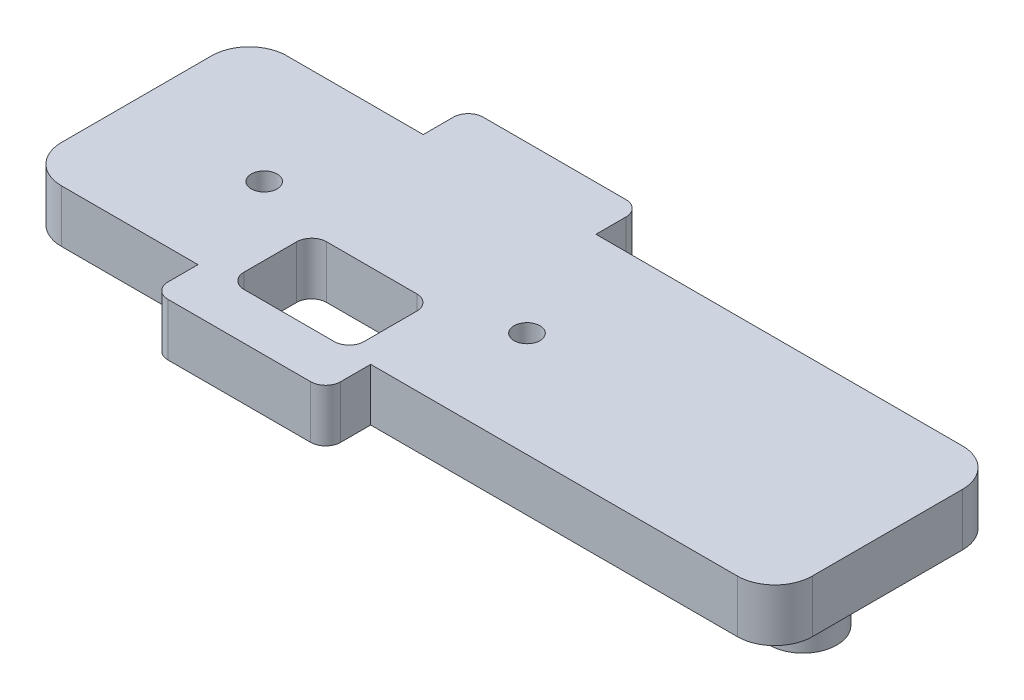
SolidWorks part; units mm, degrees
ref_plane "Front Plane" through (0, 0, 0) normal (0, 0, 1) x (1, 0, 0)
ref_plane "Top Plane" through (0, 0, 0) normal (0, 1, 0) x (1, 0, 0)
ref_plane "Right Plane" through (0, 0, 0) normal (1, 0, 0) x (0, 0, -1)
sketch "Sketch1" plane through (0, 0, 0) normal (0, 1, 0) x (1, 0, 0)
  line L1 (-45.1945, 17.8802) -> (54.8055, 17.8802)
  line L2 (-45.1945, 17.8802) -> (-45.1945, -12.1198)
  line L3 (-45.1945, -12.1198) -> (54.8055, -12.1198)
  line L4 (54.8055, 17.8802) -> (54.8055, -12.1198)
  dimension "D1" = 100
  dimension "D2" = 30
extrude "Boss-Extrude1" add sketch "Sketch1" along normal blind 7
ref_plane "Plane1" through (0, -1, 0) normal (0, -1, 0) x (-1, 0, 0)
sketch "Sketch2" plane through (0, -1, 0) normal (0, -1, 0) x (-1, 0, 0)
  line L0 (-54.8055, 2.8802) -> (57.5711, 2.8802) construction
  line L1 (-41.1646, -0.0198) -> (-44.5646, -0.0198)
  line L2 (-41.1646, -0.0198) -> (-41.1646, 5.7802)
  line L3 (-41.1646, 5.7802) -> (-44.5646, 5.7802)
  line L4 (-44.5646, -0.0198) -> (-44.5646, 5.7802)
  line L5 (-54.8055, -12.1198) -> (-54.8055, 17.8802) construction
  line L6 (-42.8646, -12.1198) -> (-42.8646, 27.765) construction
  line L8 (45.1945, -12.1198) -> (-54.8055, -12.1198) construction
  dimension "D1" = 3.4
  dimension "D2" = 5.8
  dimension "D3" = 1.7
  dimension "D4" = 2.9
extrude "Boss-Extrude2" add sketch "Sketch2" along normal blind 6 separate body
shell "Shell1" thickness 1 removed face at (42.8646, -7, -2.8802) outward yes
sketch "Sketch3" plane through (0, 0, 0) normal (0, -1, 0) x (-1, 0, 0)
  line L0 (-42.8646, -0.0198) -> (-42.8646, 11.0227) construction
  line L1 (-44.5646, -0.0198) -> (-41.1646, -0.0198) construction
  line L2 (-41.1646, 2.8802) -> (-49.8164, 2.8802) construction
  line L3 (-41.1646, -0.0198) -> (-41.1646, 5.7802) construction
  point P9 (-42.8646, 2.8802)
sketch "Sketch4" plane through (0, 0, 0) normal (0, -1, 0) x (-1, 0, 0)
  circle A0 centre (-42.9099, 3.5376) radius 4.5
  circle A1 centre (-42.9099, 3.5376) radius 3.7
extrude "Boss-Extrude3" add sketch "Sketch4" along normal blind 10
sketch "Sketch5" plane through (0, 0, 0) normal (0, -1, 0) x (-1, 0, 0)
  circle A0 centre (-42.8646, 2.8802) radius 4.25
  circle A1 centre (-42.8646, 2.8802) radius 5.5
extrude "Boss-Extrude4" add sketch "Sketch5" along normal blind 4
fillet "Fillet1" radius 5 4 edges at (-45.1945, 3.5, -17.8802) (-45.1945, 3.5, 12.1198) (54.8055, 3.5, -17.8802) (54.8055, 3.5, 12.1198)
sketch "Sketch6" plane through (0, 0, 0) normal (0, -1, 0) x (-1, 0, 0)
  line L0 (40.1945, -12.1198) -> (-49.8055, -12.1198) construction
  line L1 (22.0125, -12.1198) -> (-0.9875, -12.1198)
  line L2 (22.0125, -12.1198) -> (22.0125, -18.1198)
  line L3 (22.0125, -18.1198) -> (-0.9875, -18.1198)
  line L4 (-0.9875, -12.1198) -> (-0.9875, -18.1198)
  line L5 (45.1945, 2.8802) -> (44.2396, 2.8802) construction
  line L6 (45.1945, 12.8802) -> (45.1945, -7.1198) construction
  line L7 (22.0125, 23.8802) -> (-0.9875, 23.8802)
  line L8 (-0.9875, 17.8802) -> (-0.9875, 23.8802)
  line L9 (22.0125, 17.8802) -> (-0.9875, 17.8802)
  line L10 (22.0125, 17.8802) -> (22.0125, 23.8802)
  dimension "D1" = 6
  dimension "D2" = 23
extrude "Boss-Extrude5" add sketch "Sketch6" against normal up to surface (7 mm away) up to face at (4.8055, 7, -2.8802)
sketch "Sketch7" plane through (0, 0, 0) normal (0, -1, 0) x (-1, 0, 0)
  line L0 (40.1945, -12.1198) -> (22.0125, -12.1198) construction
  line L1 (-0.9875, -12.1198) -> (-49.8055, -12.1198) construction
  circle A0 centre (27.1973, 1.8802) radius 1.725
  circle A1 centre (-7.8027, 1.8802) radius 1.725
  dimension "D1" = 35
  dimension "D2" = 14
  dimension "D3" = 14
extrude "Cut-Extrude1" cut sketch "Sketch7" against normal up to surface (7 mm away) up to face at (-2.8535, 7, -2.8802)
fillet "Fillet2" radius 2 4 edges at (0.9875, 3.5, -23.8802) (-22.0125, 3.5, -23.8802) (0.9875, 3.5, 18.1198) (-22.0125, 3.5, 18.1198)
sketch "Sketch8" plane through (0, 0, 0) normal (0, -1, 0) x (-1, 0, 0)
  line L0 (1.0125, -18.1198) -> (20.0125, -18.1198) construction
  line L1 (18.0789, -11.9198) -> (2.0789, -11.9198)
  line L2 (18.0789, -11.9198) -> (18.0789, -0.9198)
  line L3 (18.0789, -0.9198) -> (2.0789, -0.9198)
  line L4 (2.0789, -11.9198) -> (2.0789, -0.9198)
  dimension "D1" = 16
  dimension "D2" = 11
  dimension "D3" = 6.2
extrude "Cut-Extrude2" cut sketch "Sketch8" against normal up to surface (7 mm away) up to face at (-27.1973, 7, -0.1552)
fillet "Fillet3" radius 2 4 edges at (-2.0789, 3.5, 0.9198) (-18.0789, 3.5, 0.9198) (-2.0789, 3.5, 11.9198) (-18.0789, 3.5, 11.9198)
